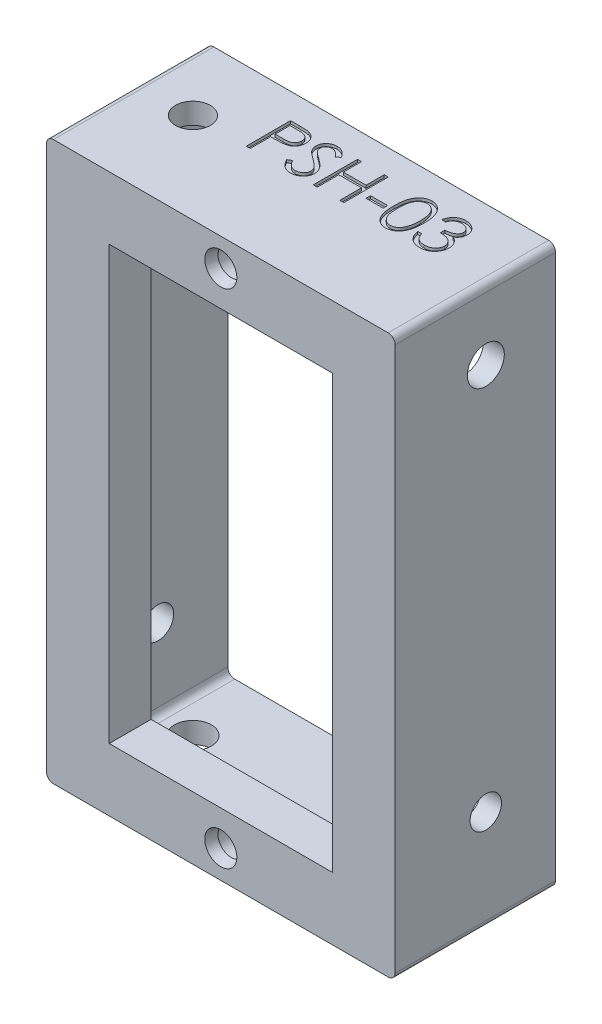
SolidWorks part; units mm, degrees
ref_plane "Front" through (0, 0, 0) normal (0, 0, 1) x (1, 0, 0)
ref_plane "Top" through (0, 0, 0) normal (0, 1, 0) x (1, 0, 0)
ref_plane "Right" through (0, 0, 0) normal (1, 0, 0) x (0, 0, -1)
sketch "Sketch3" plane through (0, 0, 0) normal (0, 0, 1) x (1, 0, 0)
  line L0 (10.9, 16.4) -> (0, 16.4) construction
  line L1 (0, 0) -> (50, 0)
  line L2 (0, 0) -> (0, 80)
  line L3 (0, 80) -> (50, 80)
  line L4 (50, 0) -> (50, 80)
  line L5 (10.9, 16.4) -> (39.1, 16.4)
  line L6 (10.9, 16.4) -> (10.9, 63.6)
  line L7 (10.9, 63.6) -> (39.1, 63.6)
  line L8 (39.1, 16.4) -> (39.1, 63.6)
  line L9 (39.1, 16.4) -> (50, 16.4) construction
  line L10 (10.9, 16.4) -> (10.9, 0) construction
  line L11 (10.9, 63.6) -> (10.9, 80) construction
  line L12 (25, 63.6) -> (25, 40) construction
  line L13 (25, 40) -> (25, 16.4) construction
  line L14 (25, 40) -> (5, 40) construction
  line L15 (25, 40) -> (45, 40) construction
  circle A0 centre (5, 40) radius 1.4
  circle A1 centre (45, 40) radius 1.4
  dimension "D5" = 40
  dimension "D6" = 2.8
  dimension "D1" = 50
  dimension "D2" = 80
  dimension "D3" = 28.2
  dimension "D4" = 47.2
extrude "Boss-Extrude1" add sketch "Sketch3" along normal blind 23
sketch "Sketch4" plane through (0, 0, 0) normal (0, 0, -1) x (-1, 0, 0)
  line L8 (-47, 3) -> (-3, 3)
  line L9 (-3, 3) -> (-3, 77)
  line L10 (-47, 77) -> (-47, 3)
  line L11 (-3, 77) -> (-47, 77)
  line L12 (-47, 3) -> (-3, 3)
  line L13 (-3, 3) -> (-3, 77)
  line L14 (-47, 77) -> (-47, 3)
  line L15 (-3, 77) -> (-47, 77)
  dimension "D1" = 3
extrude "Cut-Extrude1" cut sketch "Sketch4" against normal offset from surface (17 mm away) 6 up to face at (25, 40, 23)
chamfer "Chamfer1" distance 0.4 angle 75 2 edges at (46.4, 40, 23) (6.4, 40, 23) first distance on face at (25, 40, 23)
fillet "Fillet1" radius 1 4 edges at (0, 0, 11.5) (50, 0, 11.5) (50, 80, 11.5) (0, 80, 11.5)
fillet "Fillet2" radius 1 4 edges at (47, 3, 8.5) (3, 3, 8.5) (3, 77, 8.5) (47, 77, 8.5)
sketch "Sketch5" plane through (0, 0, 0) normal (-1, 0, 0) x (0, 0, 1)
  line L0 (0, 79) -> (0, 1) construction
  line L1 (0, 80) -> (23, 80) construction
  line L2 (10, 70) -> (10, 45) construction
  line L3 (10, 45) -> (10, 14.5) construction
  circle A0 centre (10, 70) radius 2.5
  circle A2 centre (10, 14.5) radius 2.25
  dimension "D1" = 10
  dimension "D2" = 5
  dimension "D3" = 10
  dimension "D4" = 25
  dimension "D5" = 14.5
  dimension "D6" = 4.5
extrude "Cut-Extrude2" cut sketch "Sketch5" against normal up to next
hole_wizard "M5 Clearance Hole1" positions "Sketch6" profile "Sketch7" hole size "M5" standard "ANSI Metric" end condition up to next
sketch "Sketch6" plane through (47, 0, 0) normal (-1, 0, 0) x (0, 0, 1)
  point P0 (10, 70)
sketch "Sketch7" plane through (47, 70, 10) normal (0, 1, 0) x (0, 0, 1)
  line L0 (0, 0) -> (0, 3)
  line L1 (0, 3) -> (2.65, 3)
  line L2 (2.65, 3) -> (2.65, 0)
  line L5 (2.65, 0) -> (0, 0)
  line L11 (0, -6.35) -> (0, 107.95) construction
  dimension "Thru Hole Dia." = 5.3
  dimension "Thru Hole Depth" = 3
sketch "Sketch8" plane through (0, 80, 0) normal (0, 1, 0) x (1, 0, 0)
  line L0 (49, 0) -> (1, 0) construction
  line L1 (0, -23) -> (0, 0) construction
  circle A0 centre (8, -10) radius 2.5
  dimension "D1" = 5
  dimension "D3" = 8
  dimension "D2" = 10
extrude "Cut-Extrude3" cut sketch "Sketch8" against normal up to next
hole_wizard "M5 Clearance Hole2" positions "Sketch10" profile "Sketch11" hole size "M5" standard "ANSI Metric" end condition up to next
sketch "Sketch10" plane through (0, 3, 0) normal (0, 1, 0) x (1, 0, 0)
  point P0 (8, -10)
sketch "Sketch11" plane through (8, 3, 10) normal (1, 0, 0) x (0, 0, 1)
  line L0 (0, 0) -> (0, 3)
  line L1 (0, 3) -> (2.65, 3)
  line L2 (2.65, 3) -> (2.65, 0)
  line L5 (2.65, 0) -> (0, 0)
  line L11 (0, -6.35) -> (0, 107.95) construction
  dimension "Thru Hole Dia." = 5.3
  dimension "Thru Hole Depth" = 3
sketch "Sketch12" plane through (47, 0, 0) normal (-1, 0, 0) x (0, 0, 1)
  circle A0 centre (10, 14.5) radius 2.25 construction
  circle A1 centre (10, 14.5) radius 2.25
extrude "Cut-Extrude4" cut sketch "Sketch12" against normal through all
sketch "Sketch13" plane through (0, 80, 0) normal (0, 1, 0) x (1, 0, 0)
  line L0 (8, -10) -> (50, -10) construction
  line L1 (50, 0) -> (50, -23) construction
  text T0 "PSH-03"
extrude "Cut-Extrude5" cut sketch "Sketch13" against normal blind 0.4
sketch "Sketch14" plane through (0, 0, 23) normal (0, 0, 1) x (1, 0, 0)
  line L1 (10.25, 68.5) -> (39.75, 68.5)
  line L2 (10.25, 68.5) -> (10.25, 11.5)
  line L3 (10.25, 11.5) -> (39.75, 11.5)
  line L4 (39.75, 68.5) -> (39.75, 11.5)
  line L6 (25, 68.5) -> (25, 63.6) construction
  line L7 (39.1, 63.6) -> (10.9, 63.6) construction
  line L8 (25, 11.5) -> (25, 16.4) construction
  line L9 (10.9, 16.4) -> (39.1, 16.4) construction
  dimension "D1" = 57
  dimension "D2" = 29.5
extrude "Cut-Extrude6" [suppressed] cut sketch "Sketch14" against normal through all
sketch "Sketch15" plane through (0, 0, 23) normal (0, 0, 1) x (1, 0, 0)
  line L4 (0, 79) -> (0, 1)
  line L5 (1, 0) -> (49, 0)
  line L6 (50, 1) -> (50, 79)
  line L7 (49, 80) -> (1, 80)
  line L8 (0, 79) -> (0, 1)
  line L9 (1, 0) -> (49, 0)
  line L10 (50, 1) -> (50, 79)
  line L11 (49, 80) -> (1, 80)
  arc A4 (0, 1) -> (1, 0) centre (1, 1) ccw
  arc A5 (49, 0) -> (50, 1) centre (49, 1) ccw
  arc A6 (50, 79) -> (49, 80) centre (49, 79) ccw
  arc A7 (1, 80) -> (0, 79) centre (1, 79) ccw
  arc A8 (0, 1) -> (1, 0) centre (1, 1) ccw
  arc A9 (49, 0) -> (50, 1) centre (49, 1) ccw
  arc A10 (50, 79) -> (49, 80) centre (49, 79) ccw
  arc A11 (1, 80) -> (0, 79) centre (1, 79) ccw
  dimension "D1" = 0
extrude "Boss-Extrude2" add sketch "Sketch15" against normal up to surface (6 mm away) up to face at (25, 40, 17)
sketch "Sketch16" plane through (0, 0, 23) normal (0, 0, 1) x (1, 0, 0)
  line L0 (25, 4) -> (25, 9) construction
  line L1 (9, 71) -> (41, 71)
  line L2 (9, 71) -> (9, 9)
  line L3 (9, 9) -> (41, 9)
  line L4 (41, 71) -> (41, 9)
  line L5 (25, 9) -> (25, 71) construction
  line L6 (25, 71) -> (25, 76) construction
  line L7 (9, 40) -> (0, 40) construction
  line L8 (0, 79) -> (0, 1) construction
  line L9 (41, 40) -> (50, 40) construction
  line L10 (50, 1) -> (50, 79) construction
  circle A0 centre (25, 76) radius 1.9
  circle A1 centre (25, 4) radius 1.9
  dimension "D1" = 72
  dimension "D4" = 3.8
  dimension "D2" = 62
  dimension "D3" = 32
extrude "Cut-Extrude7" cut sketch "Sketch16" against normal up to surface (6 mm away) up to face at (25, 40, 17)
chamfer "Chamfer2" distance 0.4 angle 75 2 edges at (26.9, 4, 23) (26.9, 76, 23) first distance on face at (26.9, 4, 23)
chamfer "Chamfer3" distance 0.5 angle 75 2 edges at (25, 3, 17) (25, 77, 17) first distance on face at (25, 2.55, 17) first distance on face at (25, 77.45, 17)
